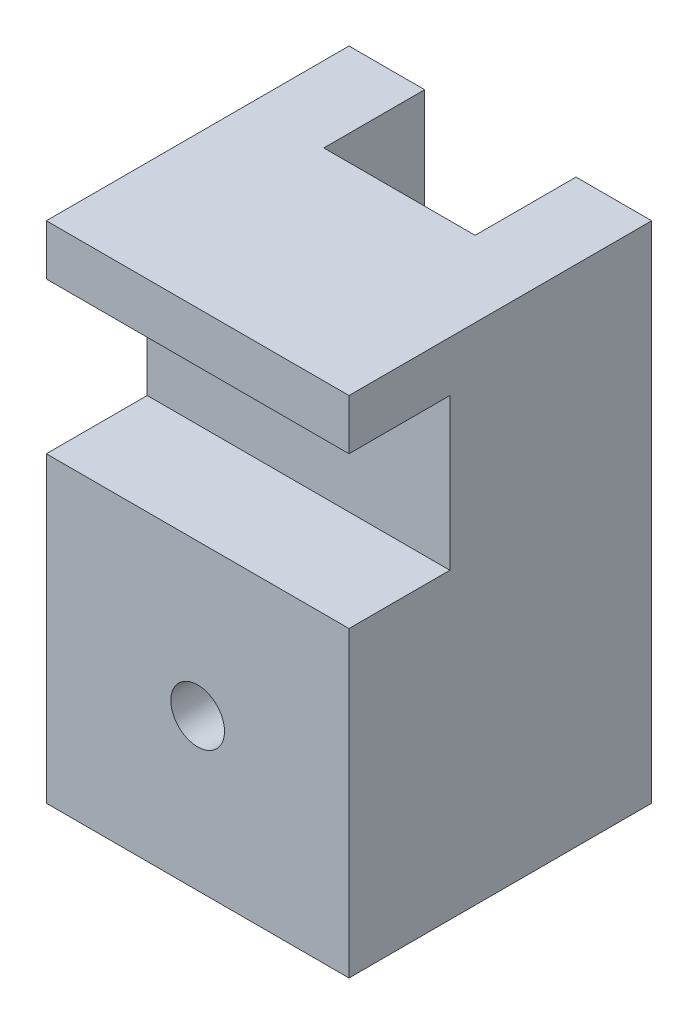
SolidWorks part; units mm, degrees
ref_plane "Front Plane" through (0, 0, 0) normal (0, 0, 1) x (1, 0, 0)
ref_plane "Top Plane" through (0, 0, 0) normal (0, 1, 0) x (1, 0, 0)
ref_plane "Right Plane" through (0, 0, 0) normal (1, 0, 0) x (0, 0, -1)
sketch "Sketch1" plane through (0, 0, 0) normal (0, 0, 1) x (1, 0, 0)
  line L1 (-19.05, -31.75) -> (19.05, -31.75)
  line L2 (-19.05, -31.75) -> (-19.05, 31.75)
  line L3 (-19.05, 31.75) -> (19.05, 31.75)
  line L4 (19.05, -31.75) -> (19.05, 31.75)
  line L5 (-19.05, -31.75) -> (19.05, 31.75) construction
  line L6 (-19.05, 31.75) -> (19.05, -31.75) construction
  point P0 (0, 0)
  dimension "D1" = 38.1
  dimension "D2" = 63.5
extrude "Boss-Extrude1" add sketch "Sketch1" along normal mid plane 38.1 contours L3 L4 L1 L2
sketch "Sketch2" plane through (0, 0, -19.05) normal (0, 0, -1) x (-1, 0, 0)
  line L0 (19.05, 31.75) -> (-19.05, 31.75) construction
  line L1 (-9.525, -31.75) -> (9.525, -31.75)
  line L2 (-9.525, -31.75) -> (-9.525, 31.75)
  line L3 (-9.525, 31.75) -> (9.525, 31.75)
  line L4 (9.525, -31.75) -> (9.525, 31.75)
  line L5 (-9.525, -31.75) -> (9.525, 31.75) construction
  line L6 (-9.525, 31.75) -> (9.525, -31.75) construction
  point P0 (0, 0)
  point P8 (0, 0)
  dimension "D1" = 19.05
extrude "Cut-Extrude1" cut sketch "Sketch2" against normal blind 12.7
sketch "Sketch3" plane through (0, 0, 19.05) normal (0, 0, 1) x (1, 0, 0)
  line L0 (0, -20.955) -> (0, 20.955) construction
  line L1 (-19.05, 6.35) -> (19.05, 6.35)
  line L2 (-19.05, 6.35) -> (-19.05, 25.4)
  line L3 (-19.05, 25.4) -> (19.05, 25.4)
  line L4 (19.05, 6.35) -> (19.05, 25.4)
  line L5 (-19.05, 6.35) -> (19.05, 25.4) construction
  line L6 (-19.05, 25.4) -> (19.05, 6.35) construction
  line L7 (19.05, -31.75) -> (19.05, 31.75) construction
  line L8 (-19.05, 31.75) -> (19.05, 31.75) construction
  point P0 (0, 15.875)
  dimension "D1" = 19.05
  dimension "D2" = 15.875
extrude "Cut-Extrude2" cut sketch "Sketch3" against normal blind 12.7
sketch "Sketch4" plane through (0, 0, 19.05) normal (0, 0, 1) x (1, 0, 0)
  line L0 (0, -20.955) -> (0, 20.955) construction
  line L2 (-19.05, -31.75) -> (19.05, -31.75) construction
  circle A0 centre (0, -12.7) radius 14.2875 construction
  point P0 (0, -12.7)
  point P1 (0, -11.1078)
  point P8 (0, 0)
  dimension "D1" = 28.575
  dimension "D2" = 19.05
hole_wizard "1/4 Clearance Hole1" positions "Sketch5" profile "Sketch6" hole size "1/4" standard "ANSI Inch" end condition through all
sketch "Sketch5" plane through (0, 0, 19.05) normal (0, 0, 1) x (1, 0, 0)
  point P0 (0, -12.7)
sketch "Sketch6" plane through (0, -12.7, 19.05) normal (1, 0, 0) x (0, -1, 0)
  line L0 (0, 0) -> (0, 38.1)
  line L1 (0, 38.1) -> (3.3782, 38.1)
  line L2 (3.3782, 38.1) -> (3.3782, 0)
  line L5 (3.3782, 0) -> (0, 0)
  line L11 (0, -6.35) -> (0, 107.95) construction
  dimension "Thru Hole Dia." = 6.7564
  dimension "Thru Hole Depth" = 38.1
sketch "Sketch7" plane through (0, 0, 6.35) normal (0, 0, 1) x (1, 0, 0)
  line L0 (0, -20.955) -> (0, 20.955) construction
  line L1 (19.05, 25.4) -> (-19.05, 25.4) construction
  point P0 (0, 15.875)
  dimension "D1" = 9.525
hole_wizard "#8-32 Tapped Hole1" positions "Sketch8" profile "Sketch9" tap size "#8-32" standard "ANSI Inch"
sketch "Sketch8" plane through (0, 0, 6.35) normal (0, 0, 1) x (1, 0, 0)
  point P0 (0, 15.875)
sketch "Sketch9" plane through (0, 15.875, 6.35) normal (1, 0, 0) x (0, -1, 0)
  line L0 (0, 0) -> (0, 11.7058)
  line L1 (0, 11.7058) -> (1.7272, 10.668)
  line L2 (1.7272, 10.668) -> (1.7272, 0)
  line L5 (1.7272, 0) -> (0, 0)
  line L10 (0, 11.7058) -> (-1.7272, 10.668) construction
  line L11 (0, -6.35) -> (0, 107.95) construction
  dimension "Tap Drill Dia." = 3.4544
  dimension "Tap Drill Depth" = 10.668
  dimension "Drill Angle" = 118
